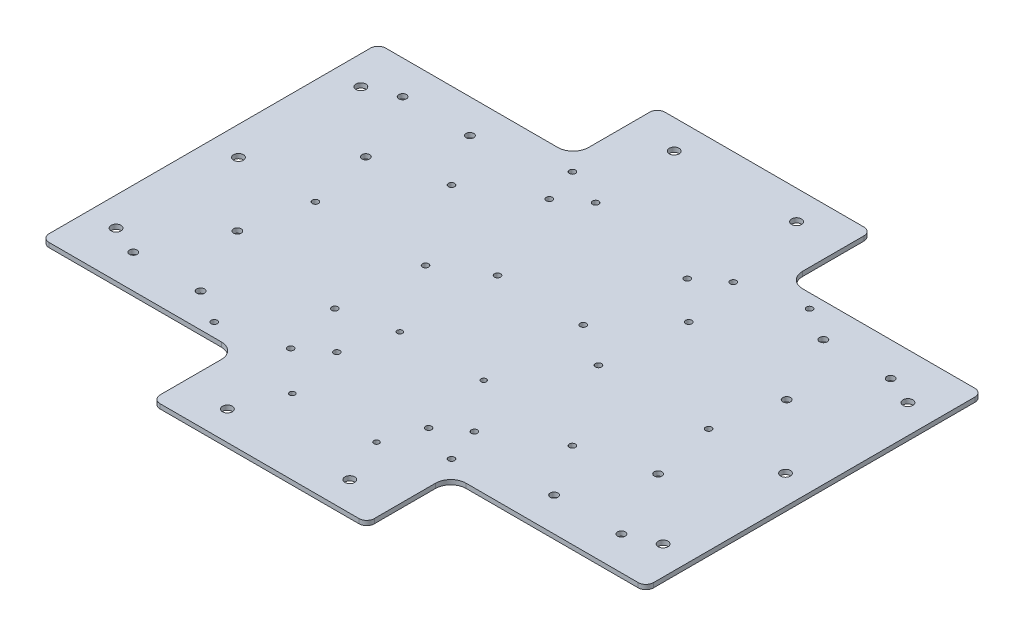
SolidWorks part; units mm, degrees
material "1060 Сплав"
ref_plane "Спереди" through (0, 0, 0) normal (0, 0, 1) x (1, 0, 0)
ref_plane "Сверху" through (0, 0, 0) normal (0, 1, 0) x (1, 0, 0)
ref_plane "Справа" through (0, 0, 0) normal (1, 0, 0) x (0, 0, -1)
sketch "Эскиз1" plane through (0, 0, 0) normal (0, 1, 0) x (1, 0, 0)
  line L1 (-65, -165) -> (65, -165)
  line L2 (-197.5, -105) -> (-197.5, 105)
  line L3 (-65, 165) -> (65, 165)
  line L4 (197.5, -105) -> (197.5, 105)
  line L5 (197.5, -105) -> (137.5, -105) construction
  line L6 (137.5, -110) -> (137.5, -66.2968) construction
  line L18 (-284.5497, 0) -> (284.3305, 0) construction
  line L19 (-160.9018, 110) -> (-134.9018, 110)
  line L39 (-70, 120) -> (-70, 160)
  line L40 (0, 262.7398) -> (0, -186.5795) construction
  line L41 (-192.5, 110) -> (-80, 110)
  line L43 (-192.5, -110) -> (-80, -110)
  line L44 (-70, -120) -> (-70, -160)
  line L45 (70, 120) -> (70, 160)
  line L46 (192.5, 110) -> (80, 110)
  line L47 (192.5, -110) -> (80, -110)
  line L48 (70, -120) -> (70, -160)
  line L54 (160.9018, -110) -> (134.9018, -110)
  line L60 (160.9018, 110) -> (134.9018, 110)
  line L65 (40, -146) -> (-40, -146) construction
  line L66 (-178.7687, -80) -> (-178.7687, 80) construction
  arc A0 (70, -120) -> (80, -110) centre (80, -120) cw
  arc A1 (70, 120) -> (80, 110) centre (80, 120) ccw
  arc A2 (-80, -110) -> (-70, -120) centre (-80, -120) cw
  arc A3 (-70, 120) -> (-80, 110) centre (-80, 120) cw
  arc A4 (192.5, -110) -> (197.5, -105) centre (192.5, -105) ccw
  arc A5 (70, -160) -> (65, -165) centre (65, -160) cw
  arc A6 (-70, -160) -> (-65, -165) centre (-65, -160) ccw
  arc A7 (-192.5, -110) -> (-197.5, -105) centre (-192.5, -105) cw
  arc A8 (-192.5, 110) -> (-197.5, 105) centre (-192.5, 105) ccw
  arc A9 (197.5, 105) -> (192.5, 110) centre (192.5, 105) ccw
  arc A10 (70, 160) -> (65, 165) centre (65, 160) ccw
  arc A11 (-70, 160) -> (-65, 165) centre (-65, 160) cw
  circle A12 centre (40, 146) radius 3.2
  circle A13 centre (40, -146) radius 3.2
  circle A14 centre (-40, -146) radius 3.2
  circle A15 centre (-40, 146) radius 3.2
  circle A16 centre (-178.7687, 80) radius 3.2
  circle A17 centre (-178.7687, -80) radius 3.2
  circle A18 centre (-178.7687, 0) radius 3.2
  circle A19 centre (178.7687, 80) radius 3.2
  circle A20 centre (178.7687, 0) radius 3.2
  circle A21 centre (178.7687, -80) radius 3.2
  circle A22 centre (137.5, -42) radius 2.5
  circle A23 centre (159.5, -88) radius 2.5
  circle A24 centre (115.5, -88) radius 2.5
  circle A25 centre (-159.5, -88) radius 2.5
  circle A26 centre (-137.5, -42) radius 2.5
  circle A27 centre (-115.5, -88) radius 2.5
  circle A28 centre (159.5, 88) radius 2.5
  circle A29 centre (137.5, 42) radius 2.5
  circle A30 centre (115.5, 88) radius 2.5
  circle A31 centre (-115.5, 88) radius 2.5
  circle A32 centre (-137.5, 42) radius 2.5
  circle A33 centre (-159.5, 88) radius 2.5
  point P0 (0, 0)
  point P3 (70, -110)
  point P17 (-147.9018, 110)
  point P18 (-147.9018, 110)
  point P46 (70, 110)
  point P52 (-70, -110)
  point P55 (-70, 110)
  point P56 (-147.9018, 0)
  point P59 (-178.7687, 0)
  point P62 (178.7687, 80)
  point P77 (197.5, -110)
  point P80 (70, -165)
  point P83 (-70, -165)
  point P86 (-197.5, -110)
  point P89 (-197.5, 110)
  point P92 (197.5, 110)
  point P95 (70, 165)
  point P98 (-70, 165)
  point P99 (178.7687, 0)
  point P100 (40, 146)
  point P101 (178.7687, -80)
  point P103 (-40, 146)
  dimension "D2" = 19
  dimension "D6" = 10
  dimension "D11" = 40
  dimension "D12" = 40
  dimension "D4" = 5
  dimension "D17" = 5
  dimension "D9" = 6.4
  dimension "D3" = 38
  dimension "D14" = 5
  dimension "D5" = 330
  dimension "D7" = 395
  dimension "D8" = 68
  dimension "D10" = 60
  dimension "D13" = 22
  dimension "D15" = 80
  dimension "D16" = 80
  dimension "D18" = 18.7313
  dimension "D19" = 19
extrude "Бобышка-Вытянуть1" add sketch "Эскиз1" along normal blind 3 separate body contours A11 L39 A3 L41 L43 A2 L44 A6 L1 A5 L48 A0 L47 L46 A1 L45 A10 L3 | L4 A9 L46 L47 A4 | L46 | L47 | L41 A8 L2 A7 L43 | L19 region at (0, 0, 0)
sketch "Эскиз2" plane through (0, 3, 0) normal (0, 1, 0) x (1, 0, 0)
  line L0 (197.5, 0) -> (-197.5, 0) construction
  line L1 (197.5, -105) -> (197.5, 105) construction
  line L2 (-197.5, -105) -> (-197.5, 105) construction
  line L3 (0, 165) -> (0, -165) construction
  line L4 (-65, 165) -> (65, 165) construction
  line L5 (-65, -165) -> (65, -165) construction
  line L6 (192.5, 110) -> (80, 110) construction
  circle A0 centre (128.5, 0) radius 2
  circle A1 centre (56.5, 0) radius 2
  circle A2 centre (93.5, 101) radius 2
  circle A3 centre (61.5, 54) radius 2
  circle A4 centre (49.5, 74) radius 2 construction
  circle A5 centre (53.5, 91.0922) radius 2
  circle A6 centre (36.503, 78.0468) radius 2
  circle A7 centre (28.6809, 17.8719) radius 2
  circle A8 centre (-27.3191, 17.8719) radius 2
  circle A9 centre (27.4963, -46.0223) radius 1.75
  circle A10 centre (93.5, -54.0533) radius 2
  circle A11 centre (61.5, -101.043) radius 2
  circle A12 centre (53.5, -78.0725) radius 2
  circle A13 centre (36.503, -90.9991) radius 2
  circle A14 centre (27.4963, -116.0332) radius 1.75
  circle A15 centre (-27.5526, -116.0332) radius 1.75
  circle A16 centre (-27.3191, -46) radius 1.75
  circle A17 centre (-53.6363, -90.9991) radius 2
  circle A18 centre (-36.4017, -78.0725) radius 2
  circle A19 centre (-93.5268, -101.043) radius 2
  circle A20 centre (-61.7277, -54.0533) radius 2
  circle A21 centre (-36.4017, 91.0922) radius 2
  circle A22 centre (-53.6363, 78.0468) radius 2
  circle A23 centre (-61.5417, 101) radius 2
  circle A24 centre (-93.5268, 54) radius 2
  circle A25 centre (-128.5, 0) radius 2
  circle A26 centre (-56.5, 0) radius 2
  point P15 (97.5, 105)
  point P19 (57.5, 50)
  point P24 (53.5, 101)
  point P25 (52.5, 81)
  dimension "D1" = 69
  dimension "D2" = 4
  dimension "D6" = 4
  dimension "D11" = 4
  dimension "D16" = 4
  dimension "D4" = 100
  dimension "D5" = 5
  dimension "D7" = 4
  dimension "D8" = 4
  dimension "D9" = 51
  dimension "D10" = 36
  dimension "D12" = 4
  dimension "D13" = 4
  dimension "D14" = 31
  dimension "D15" = 1
  dimension "D17" = 7
  dimension "D18" = 3
  dimension "D3" = 2
extrude "Вырез-Вытянуть1" cut sketch "Эскиз2" against normal blind 10
